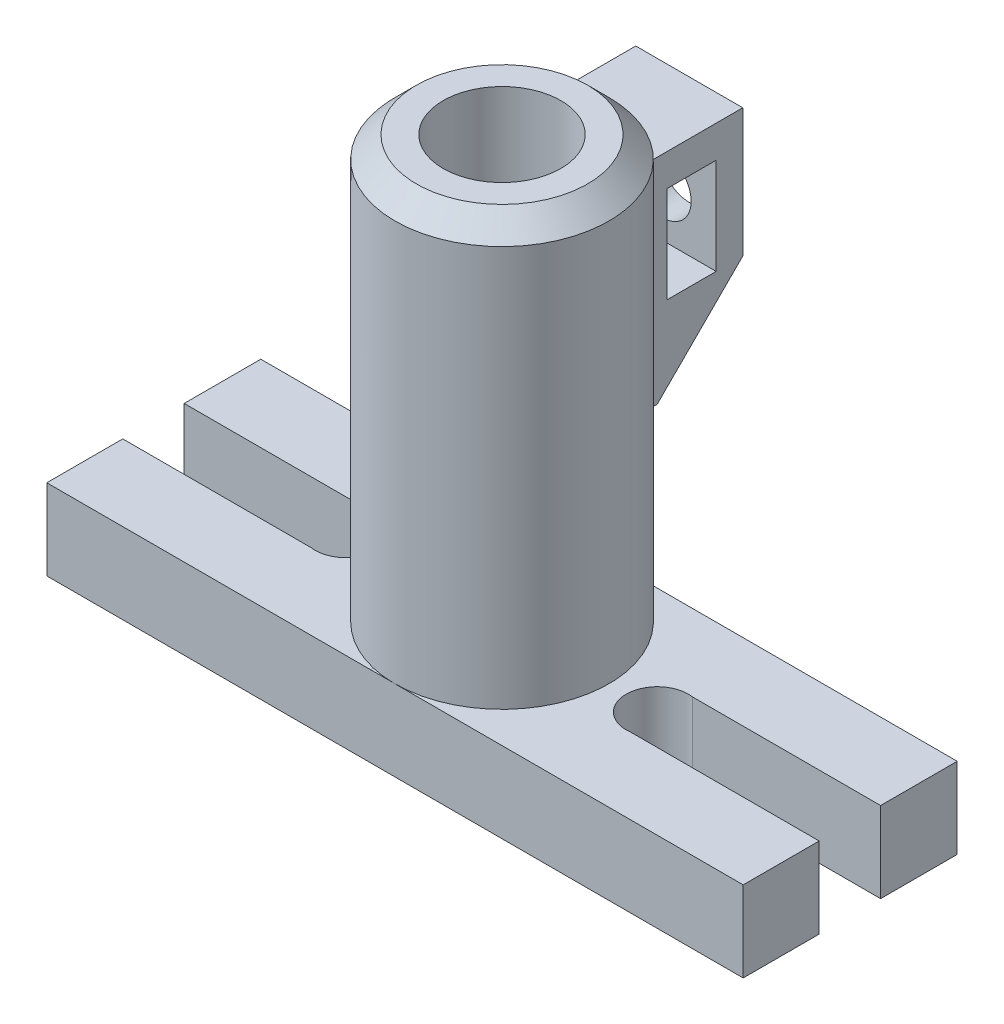
SolidWorks part; units mm, degrees
ref_plane "Front Plane" through (0, 0, 0) normal (0, 0, 1) x (1, 0, 0)
ref_plane "Top Plane" through (0, 0, 0) normal (0, 1, 0) x (1, 0, 0)
ref_plane "Right Plane" through (0, 0, 0) normal (1, 0, 0) x (0, 0, -1)
sketch "Sketch1" plane through (0, 0, 0) normal (0, 1, 0) x (1, 0, 0)
  line L1 (-41.3258, -12.7) -> (41.3258, -12.7)
  line L2 (-41.3258, -12.7) -> (-41.3258, 12.7)
  line L3 (-41.3258, 12.7) -> (41.3258, 12.7)
  line L4 (41.3258, -12.7) -> (41.3258, 12.7)
  line L5 (-41.3258, -12.7) -> (41.3258, 12.7) construction
  line L6 (-41.3258, 12.7) -> (41.3258, -12.7) construction
  point P0 (0, 0)
  dimension "D1" = 82.6516
  dimension "D2" = 25.4
extrude "Boss-Extrude1" add sketch "Sketch1" along normal blind 9.5758
sketch "Sketch8" plane through (0, 0, 12.7) normal (0, 0, 1) x (1, 0, 0)
  line L1 (0, 0) -> (-2.9028, 0)
  line L2 (0, 0) -> (0, 9.5801)
  line L3 (0, 9.5801) -> (-2.9028, 9.5801)
  line L4 (-2.9028, 0) -> (-2.9028, 9.5801)
extrude "Boss-Extrude4" add sketch "Sketch8" against normal through all
sketch "Sketch10" plane through (0, 9.5758, 0) normal (0, 1, 0) x (1, 0, 0)
  circle A0 centre (0, 0) radius 12.7
extrude "Boss-Extrude5" add sketch "Sketch10" along normal blind 50.1015
sketch "Sketch12" plane through (0, 59.6773, 0) normal (0, 1, 0) x (1, 0, 0)
  circle A0 centre (0, 0) radius 6.985
  dimension "D1" = 13.97
extrude "Cut-Extrude2" cut sketch "Sketch12" against normal blind 50.8635
chamfer "Chamfer1" distance 2.54 angle 45 1 edges at (0, 59.6773, 12.7)
ref_plane "Plane1" through (0, 0, -6.985) normal (0, 0, 1) x (1, 0, 0)
sketch "Sketch14" plane through (0, 0, -6.985) normal (0, 0, 1) x (1, 0, 0)
  line L1 (6.35, 29.0908) -> (-6.35, 29.0908)
  line L2 (6.35, 29.0908) -> (6.35, 54.4908)
  line L3 (6.35, 54.4908) -> (-6.35, 54.4908)
  line L4 (-6.35, 29.0908) -> (-6.35, 54.4908)
  line L5 (6.35, 29.0908) -> (-6.35, 54.4908) construction
  line L6 (6.35, 54.4908) -> (-6.35, 29.0908) construction
  point P0 (0, 41.7908)
  dimension "D1" = 12.7
  dimension "D2" = 25.4
extrude "Boss-Extrude6" add sketch "Sketch14" against normal blind 15.24
sketch "Sketch18" plane through (6.35, 0, 0) normal (1, 0, 0) x (0, 0, -1)
  line L1 (13.2284, 39.2508) -> (19.0704, 39.2508)
  line L2 (13.2284, 39.2508) -> (13.2284, 50.6808)
  line L3 (13.2284, 50.6808) -> (19.0704, 50.6808)
  line L4 (19.0704, 39.2508) -> (19.0704, 50.6808)
  line L5 (13.2284, 39.2508) -> (19.0704, 50.6808) construction
  line L6 (13.2284, 50.6808) -> (19.0704, 39.2508) construction
  line L7 (22.225, 54.4908) -> (10.9985, 54.4908) construction
  point P0 (16.1494, 44.9658)
  dimension "D1" = 11.43
  dimension "D2" = 5.842
  dimension "D3" = 3.81
  dimension "D4" = 3.81
extrude "Cut-Extrude3" cut sketch "Sketch18" against normal up to next
hole_wizard "1/4 Clearance Hole2" positions "Sketch20" profile "Sketch19" hole size "1/4" standard "ANSI Inch"
sketch "Sketch20" plane through (0, 0, -22.225) normal (0, 0, -1) x (-1, 0, 0)
  line L0 (6.35, 54.4908) -> (-6.35, 54.4908) construction
  line L1 (-6.35, 29.0908) -> (6.35, 29.0908) construction
  point P0 (0, 44.9658)
  dimension "D1" = 9.525
  dimension "D2" = 15.875
sketch "Sketch19" plane through (0, 44.9658, -22.225) normal (1, 0, 0) x (0, 1, 0)
  line L0 (0, 0) -> (0, 22.3498)
  line L1 (0, 22.3498) -> (3.3782, 20.32)
  line L2 (3.3782, 20.32) -> (3.3782, 0)
  line L5 (3.3782, 0) -> (0, 0)
  line L10 (0, 22.3498) -> (-3.3782, 20.32) construction
  line L11 (0, -6.35) -> (0, 107.95) construction
  dimension "Hole Dia." = 6.7564
  dimension "Hole Depth" = 20.32
  dimension "Drill Angle" = 118
chamfer "Chamfer2" distance 10.16 angle 45 1 edges at (0, 29.0908, -22.225)
sketch "Sketch21" plane through (0, 59.6773, 0) normal (0, 1, 0) x (1, 0, 0)
  line L1 (-52.2341, 32.5275) -> (49.937, 32.5275)
  line L2 (-52.2341, 32.5275) -> (-52.2341, -26.4981)
  line L3 (-52.2341, -26.4981) -> (49.937, -26.4981)
  line L4 (49.937, 32.5275) -> (49.937, -26.4981)
extrude "Cut-Extrude4" [suppressed] cut sketch "Sketch21" against normal blind 50.8
sketch "Sketch22" plane through (0, 0, 0) normal (1, 0, 0) x (0, 0, -1)
  line L1 (16.4624, 11.6654) -> (-17.2995, 11.6654)
  line L2 (16.4624, 11.6654) -> (16.4624, -3.6252)
  line L3 (16.4624, -3.6252) -> (-17.2995, -3.6252)
  line L4 (-17.2995, 11.6654) -> (-17.2995, -3.6252)
extrude "Cut-Extrude5" [suppressed] cut sketch "Sketch22" against normal through all
sketch "Sketch2" plane through (0, 9.5758, 0) normal (0, 1, 0) x (1, 0, 0)
  line L0 (18.4658, -3.683) -> (41.3258, -3.683)
  line L1 (18.4658, -3.683) -> (18.4658, 3.6068)
  line L2 (41.3258, -3.683) -> (41.3258, 3.6068)
  line L3 (18.4658, 3.6068) -> (41.3258, 3.6068)
  line L4 (18.4658, -3.683) -> (41.3258, 3.6068) construction
  line L5 (41.3258, -3.683) -> (18.4658, 3.6068) construction
  line L6 (-41.3258, -12.7) -> (-2.9028, -12.7) construction
  line L7 (41.3258, 12.7) -> (0, 12.7) construction
  point P1 (29.8958, -0.0381)
  dimension "D1" = 7.2898
  dimension "D2" = 22.86
  dimension "D3" = 9.017
  dimension "D4" = 9.0932
extrude "Cut-Extrude1" cut sketch "Sketch2" against normal through all
sketch "Sketch23" plane through (0, 9.5758, 0) normal (0, 1, 0) x (1, 0, 0)
  line L0 (18.4658, 3.6068) -> (18.4658, -3.683) construction
  circle A0 centre (18.4658, -0.0381) radius 3.683
  dimension "D1" = 7.366
extrude "Cut-Extrude6" cut sketch "Sketch23" against normal through all
mirror "Mirror1" about plane through (0, 0, 0) normal (1, 0, 0) of "Cut-Extrude6", "Cut-Extrude1"
